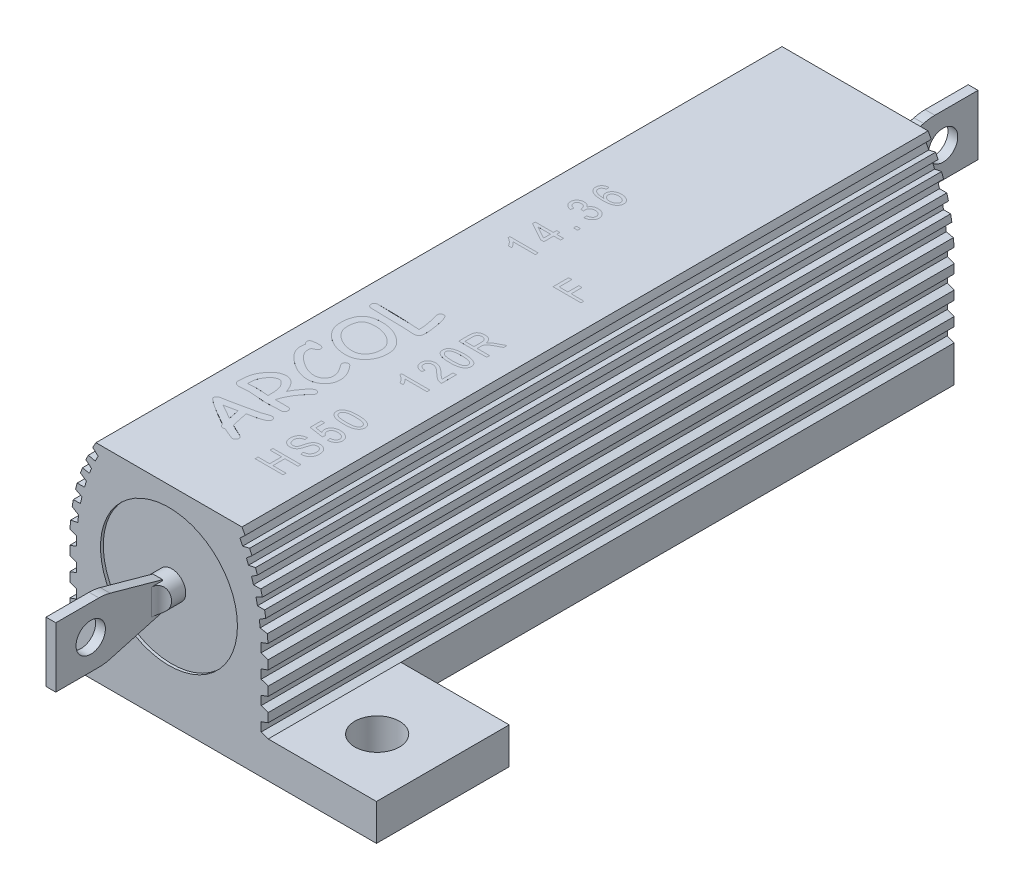
SolidWorks part; units mm, degrees
ref_plane "Front Plane" through (0, 0, 0) normal (0, 0, 1) x (1, 0, 0)
ref_plane "Top Plane" through (0, 0, 0) normal (0, 1, 0) x (1, 0, 0)
ref_plane "Right Plane" through (0, 0, 0) normal (1, 0, 0) x (0, 0, -1)
sketch "Sketch1" plane through (0, 0, 0) normal (0, 0, 1) x (1, 0, 0)
  line L0 (0, 0) -> (0, 14.8) construction
  line L1 (-14.85, 2.6) -> (-7.1, 2.6)
  line L2 (-14.85, 2.6) -> (-14.85, 0)
  line L3 (-14.85, 0) -> (14.85, 0)
  line L4 (14.85, 2.6) -> (14.85, 0)
  line L5 (-7.1, 14.8) -> (7.1, 14.8)
  line L6 (-7.1, 14.8) -> (-7.1, 2.6)
  line L7 (7.1, 2.6) -> (14.85, 2.6)
  line L8 (7.1, 14.8) -> (7.1, 2.6)
  dimension "D1" = 29.7
  dimension "D2" = 2.6
  dimension "D3" = 14.2
  dimension "D4" = 14.8
extrude "Boss-Extrude1" add sketch "Sketch1" along normal mid plane 49.1
sketch "Sketch2" plane through (0, 2.6, 0) normal (0, 1, 0) x (1, 0, 0)
  line L0 (-7.1, 24.55) -> (-14.85, 24.55) construction
  line L1 (0, 0) -> (0, 26.1083) construction
  circle A0 centre (10.7, -20.35) radius 1.6
  circle A1 centre (-10.7, 19.35) radius 1.6
  circle A2 centre (10.7, 19.35) radius 1.6 construction
  dimension "D1" = 39.7
  dimension "D2" = 3.2
  dimension "D3" = 21.4
  dimension "D4" = 5.2
extrude "holes" cut sketch "Sketch2" against normal through all
sketch "Sketch3" plane through (0, 2.6, 0) normal (0, 1, 0) x (1, 0, 0)
  line L0 (-7.1, -24.55) -> (-7.1, 24.55) construction
  line L1 (-14.85, -24.55) -> (-7.1, -24.55)
  line L2 (-14.85, -24.55) -> (-14.85, 15.05)
  line L3 (-14.85, 15.05) -> (-7.1, 15.05)
  line L4 (-7.1, -24.55) -> (-7.1, 15.05)
  line L5 (7.1, -24.55) -> (7.1, 24.55) construction
  line L6 (14.85, 24.55) -> (7.1, 24.55)
  line L7 (14.85, 24.55) -> (14.85, -15.05)
  line L8 (14.85, -15.05) -> (7.1, -15.05)
  line L9 (7.1, 24.55) -> (7.1, -15.05)
  line L10 (-7.1, 24.55) -> (-14.85, 24.55) construction
  dimension "D1" = 9.5
extrude "Cut-Extrude2" cut sketch "Sketch3" against normal through all
sketch "Sketch4" plane through (0, 0, 24.55) normal (0, 0, 1) x (1, 0, 0)
  line L0 (-7.1, 0) -> (14.85, 0) construction
  circle A0 centre (0, 8.5) radius 4.9
  dimension "D1" = 8.5
  dimension "D2" = 9.8
extrude "Cut-Extrude3" cut sketch "Sketch4" against normal blind 0.2
sketch "Sketch5" plane through (0, 0, 24.35) normal (0, 0, 1) x (1, 0, 0)
  circle A0 centre (0, 8.5) radius 1
  circle A1 centre (0, 8.5) radius 4.9 construction
  dimension "D1" = 2
extrude "Boss-Extrude2" add sketch "Sketch5" along normal blind 1
sketch "Sketch6" plane through (0, 0, 0) normal (1, 0, 0) x (0, 0, -1)
  line L0 (-25.35, 8.5) -> (-33, 8.5) construction
  line L1 (-25.35, 9.5) -> (-25.35, 7.5) construction
  line L2 (-33, 6.35) -> (-33, 10.65)
  line L3 (-33, 10.65) -> (-29.9146, 10.65)
  line L4 (-29.1148, 10.5414) -> (-25.35, 9.5)
  line L5 (-25.35, 9.5) -> (-25.35, 7.5)
  line L7 (-24.35, 9.5) -> (-25.35, 9.5) construction
  line L8 (-33, 6.35) -> (-29.9146, 6.35)
  line L9 (-29.1148, 6.4586) -> (-25.35, 7.5)
  arc A0 (-29.9146, 10.65) -> (-29.1148, 10.5414) centre (-29.9146, 7.65) cw
  arc A1 (-29.9146, 6.35) -> (-29.1148, 6.4586) centre (-29.9146, 9.35) ccw
  dimension "D1" = 3
  dimension "D2" = 4.3
  dimension "D3" = 33
  dimension "D4" = 15.462
extrude "Boss-Extrude3" add sketch "Sketch6" along normal mid plane 0.7
fillet "Fillet1" radius 0.8 2 edges at (0.35, 8.5, 25.35) (-0.35, 8.5, 25.35)
sketch "Sketch7" plane through (0.35, 0, 0) normal (1, 0, 0) x (0, 0, -1)
  line L0 (-26.15, 8.5) -> (-30.5, 8.5) construction
  line L1 (-26.15, 7.5633) -> (-26.15, 9.4367) construction
  line L2 (-33, 10.65) -> (-33, 6.35) construction
  circle A0 centre (-30.5, 8.5) radius 1.05
  dimension "D1" = 2.1
  dimension "D2" = 2.5
extrude "Cut-Extrude4" cut sketch "Sketch7" against normal through all
mirror "Mirror1" about plane through (0, 0, 0) normal (0, 0, 1) of "Cut-Extrude4", "Fillet1", "Boss-Extrude3", "Boss-Extrude2", "Cut-Extrude3"
sketch "Sketch8" plane through (0, 0, 24.55) normal (0, 0, 1) x (1, 0, 0)
  line L0 (0, 0) -> (0, 17.0904) construction
  line L1 (-7.1, 14.8) -> (-7.1, 0) construction
  line L2 (-7.1, 7.8) -> (-9.0103, 7.8)
  line L3 (-9.0103, 7.8) -> (-9.0103, 14.8)
  line L4 (-9.0103, 14.8) -> (-5.2244, 14.8)
  line L5 (7.1, 14.8) -> (-7.1, 14.8) construction
  line L6 (9.0103, 14.8) -> (5.2244, 14.8)
  line L7 (9.0103, 7.8) -> (9.0103, 14.8)
  line L8 (7.1, 7.8) -> (9.0103, 7.8)
  arc A0 (-5.2244, 14.8) -> (-7.1, 7.8) centre (6.9, 7.8) ccw
  arc A1 (5.2244, 14.8) -> (7.1, 7.8) centre (-6.9, 7.8) cw
  dimension "D1" = 28
  dimension "D2" = 7
  dimension "D3" = 10.4487
extrude "Cut-Extrude5" cut sketch "Sketch8" against normal up to surface (49.1 mm away) up to face at (-4.95, 5.8, -24.55)
sketch "Sketch9" plane through (0, 0, 24.55) normal (0, 0, 1) x (1, 0, 0)
  line L0 (-7.1, 2.6) -> (-6.6, 2.782)
  line L1 (-6.6, 2.782) -> (-6.6, 3.418)
  line L2 (-6.6, 3.418) -> (-7.1, 3.6)
  line L3 (-7.1, 7.8) -> (-7.1, 0) construction
  line L4 (-6.6, 3.1) -> (-7.1, 3.1) construction
  line L5 (-7.1, 3.6) -> (-7.1, 4.236)
  line L6 (-7.1, 4.236) -> (-6.6, 4.418)
  line L7 (-6.6, 4.418) -> (-6.6, 5.054)
  line L8 (-6.6, 5.054) -> (-7.1, 5.236)
  line L9 (-7.1, 5.236) -> (-7.1, 5.8721)
  line L10 (-7.1, 5.8721) -> (-6.6, 6.054)
  line L11 (-6.6, 6.054) -> (-6.6, 6.6901)
  line L12 (-6.6, 6.6901) -> (-7.1, 6.8721)
  line L13 (-7.1, 6.8721) -> (-7.1, 7.5081)
  line L14 (-7.1, 7.5081) -> (-6.6, 7.6901)
  line L15 (-6.6, 7.6901) -> (-6.6, 8.3261)
  line L16 (-6.6, 8.3261) -> (-7.0824, 8.5017)
  line L17 (-5.2244, 14.8) -> (-10.975, 14.8)
  line L18 (-10.975, 14.8) -> (-10.975, 2.6)
  line L19 (-7.1, 2.6) -> (-14.85, 2.6) construction
  line L20 (-10.975, 2.6) -> (-7.1, 2.6)
  line L21 (-7.0402, 9.0928) -> (-6.5275, 9.1972)
  line L22 (-6.466, 9.6972) -> (-6.9279, 9.9882)
  line L23 (-6.8434, 10.4682) -> (-6.3337, 10.4682)
  line L24 (-6.6861, 11.179) -> (-6.2278, 10.9482)
  line L25 (-6.5662, 11.629) -> (-6.0463, 11.6267)
  line L26 (-6.3337, 12.3683) -> (-5.9047, 12.0767)
  line L27 (-5.6934, 12.6637) -> (-6.1907, 12.7631)
  line L28 (-5.5408, 13.0419) -> (-5.9405, 13.3786)
  line L29 (-5.7711, 13.7535) -> (-5.273, 13.6368)
  line L31 (-5.4524, 14.3893) -> (-5.0732, 14.0363)
  line L39 (-4.325, 15.3) -> (-11.475, 15.3) construction
  line L40 (-11.475, 15.3) -> (-11.475, 2.1) construction
  line L41 (-11.475, 2.1) -> (-7.0118, 2.1) construction
  line L42 (-6.1, 8.6762) -> (-6.5596, 8.8435) construction
  line L43 (-6.1, 7.34) -> (-6.1, 8.6762) construction
  line L44 (-6.1, 5.7039) -> (-6.1, 7.0402) construction
  line L45 (-6.5118, 7.1901) -> (-6.1, 7.34) construction
  line L46 (-6.1, 7.0402) -> (-6.5118, 7.1901) construction
  line L47 (-6.5118, 7.1901) -> (-6.5118, 7.1901) construction
  line L48 (-6.5118, 5.554) -> (-6.1, 5.7039) construction
  line L49 (-6.5118, 5.554) -> (-6.5118, 5.554) construction
  line L50 (-6.1, 5.4041) -> (-6.5118, 5.554) construction
  line L51 (-6.1, 4.0679) -> (-6.1, 5.4041) construction
  line L52 (-6.5118, 3.918) -> (-6.1, 4.0679) construction
  line L53 (-6.5118, 3.918) -> (-6.5118, 3.918) construction
  line L54 (-6.1, 3.7681) -> (-6.5118, 3.918) construction
  line L55 (-6.1, 2.4319) -> (-6.1, 3.7681) construction
  line L56 (-7.0118, 2.1) -> (-6.1, 2.4319) construction
  arc A0 (-5.2244, 14.8) -> (-5.4524, 14.3893) centre (6.9, 7.8) ccw
  arc A1 (-5.2244, 14.8) -> (-7.1, 7.8) centre (6.9, 7.8) ccw construction
  arc A2 (-5.0732, 14.0363) -> (-5.273, 13.6368) centre (6.9, 7.8) ccw
  arc A3 (-7.0402, 9.0928) -> (-7.0824, 8.5017) centre (6.9, 7.8) ccw
  arc A4 (-4.325, 15.3) -> (-6.5596, 8.8435) centre (6.9, 7.8) ccw construction
  arc A5 (-6.466, 9.6972) -> (-6.5275, 9.1972) centre (6.9, 7.8) ccw
  arc A6 (-5.2244, 14.8) -> (-7.0824, 8.5017) centre (6.9, 7.8) ccw construction
  arc A7 (-6.8434, 10.4682) -> (-6.9279, 9.9882) centre (6.9, 7.8) ccw
  arc A8 (-6.2278, 10.9482) -> (-6.3337, 10.4682) centre (6.9, 7.8) ccw
  arc A9 (-6.5662, 11.629) -> (-6.6861, 11.179) centre (6.9, 7.8) ccw
  arc A10 (-5.9047, 12.0767) -> (-6.0463, 11.6267) centre (6.9, 7.8) ccw
  arc A11 (-6.1907, 12.7631) -> (-6.3337, 12.3683) centre (6.9, 7.8) ccw
  arc A12 (-5.5408, 13.0419) -> (-5.6934, 12.6637) centre (6.9, 7.8) ccw
  arc A13 (-5.7711, 13.7535) -> (-5.9405, 13.3786) centre (6.9, 7.8) ccw
  dimension "D4" = 0.5
  dimension "D5" = 0.5
  dimension "D1" = 0.5
  dimension "D2" = 1
  dimension "D3" = 40
  dimension "D6" = 0.48
  dimension "D7" = 0.48
  dimension "D8" = 0.45
  dimension "D9" = 0.45
extrude "Cut-Extrude6" cut sketch "Sketch9" against normal up to surface (49.1 mm away) up to face at (-3.7125, 6.3309, -24.55)
mirror "Mirror2" about plane through (0, 0, 0) normal (1, 0, 0) of "Cut-Extrude6"
sketch "Sketch10" plane through (0, 14.8, 0) normal (0, 1, 0) x (1, 0, 0)
  line L0 (-0.415, -20.0289) -> (-0.415, -3.7718) construction
  line L1 (3.4633, -20.0289) -> (3.4633, 5.5787) construction
  line L2 (-1.1588, 2.1785) -> (-1.1588, 14.451) construction
  text T0 "ARCOL" font "Comic Sans MS" height 3.5
  text T1 "14.36" font "Arial Narrow" height 2
  text T2 "HS50   120R     F" font "Arial Narrow" height 2
extrude "TEXT" add sketch "Sketch10" along normal blind 0.0001
